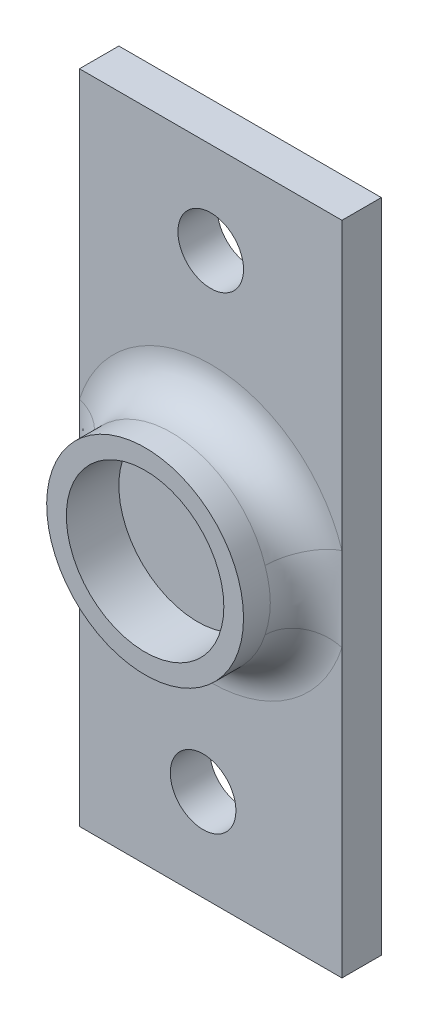
SolidWorks part; units mm, degrees
ref_plane "前视基准面" through (0, 0, 0) normal (0, 0, 1) x (1, 0, 0)
ref_plane "上视基准面" through (0, 0, 0) normal (0, 1, 0) x (1, 0, 0)
ref_plane "右视基准面" through (0, 0, 0) normal (1, 0, 0) x (0, 0, -1)
sketch "草图1" plane through (0, 0, 0) normal (0, 0, 1) x (1, 0, 0)
  line L1 (10, -25) -> (-10, -25)
  line L2 (10, -25) -> (10, 25)
  line L3 (10, 25) -> (-10, 25)
  line L4 (-10, -25) -> (-10, 25)
  line L5 (10, -25) -> (-10, 25) construction
  line L6 (10, 25) -> (-10, -25) construction
  point P0 (0, 0)
  dimension "D1" = 20
  dimension "D2" = 50
extrude "凸台-拉伸1" add sketch "草图1" along normal blind 3
sketch "草图2" plane through (0, 0, 3) normal (0, 0, 1) x (1, 0, 0)
  circle A0 centre (0, 0) radius 7.5
  dimension "D1" = 15
extrude "凸台-拉伸2" add sketch "草图2" along normal blind 5
sketch "草图3" plane through (0, 0, 8) normal (0, 0, 1) x (1, 0, 0)
  circle A0 centre (0, 0) radius 6
  dimension "D1" = 12
extrude "切除-拉伸1" cut sketch "草图3" against normal blind 4
sketch "草图4" plane through (0, 0, 3) normal (0, 0, 1) x (1, 0, 0)
  circle A0 centre (0, 18) radius 2.5
  circle A1 centre (-0.5807, -18) radius 2.5
  dimension "D1" = 5
  dimension "D2" = 5
  dimension "D3" = 18
  dimension "D4" = 18
extrude "切除-拉伸2" cut sketch "草图4" against normal blind 3
sketch "草图6" plane through (0, 0, 8) normal (0, 0, 1) x (1, 0, 0)
  circle A0 centre (0, 0) radius 7.5 construction
  circle A1 centre (0, 0) radius 7.5
  circle A2 centre (0, 0) radius 6 construction
  circle A3 centre (0, 0) radius 6
fillet "圆角2" radius 3 1 edges at (7.5, 0, 3)
